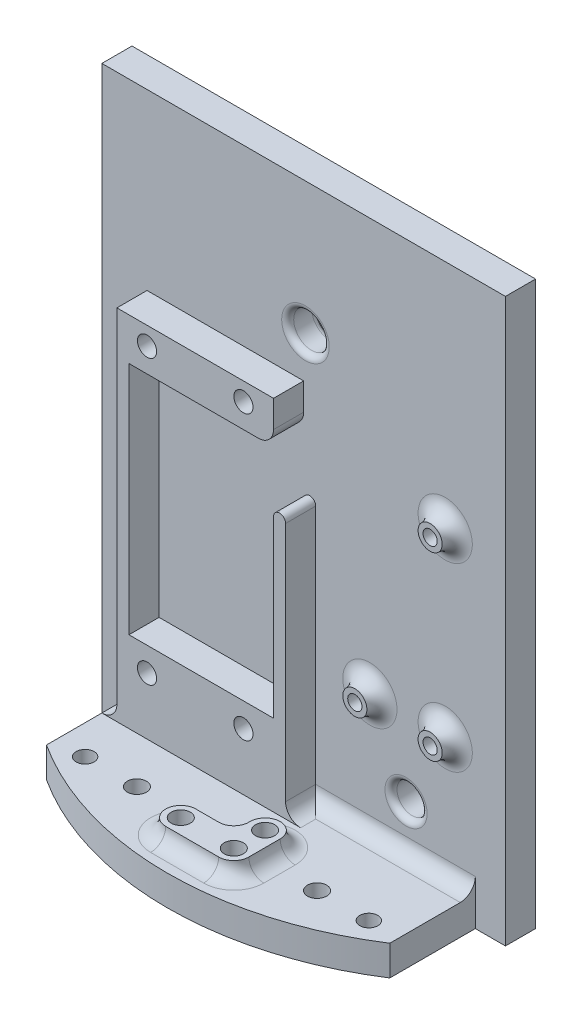
SolidWorks part; units mm, degrees
ref_plane "Front Plane" through (0, 0, 0) normal (0, 0, 1) x (1, 0, 0)
ref_plane "Top Plane" through (0, 0, 0) normal (0, 1, 0) x (1, 0, 0)
ref_plane "Right Plane" through (0, 0, 0) normal (1, 0, 0) x (0, 0, -1)
sketch "Sketch2" plane through (0, 0, 0) normal (0, 0, 1) x (1, 0, 0)
  line L1 (0, 0) -> (85.09, 0)
  line L2 (0, 0) -> (0, 118.618)
  line L3 (0, 118.618) -> (85.09, 118.618)
  line L4 (85.09, 0) -> (85.09, 118.618)
  dimension "D1" = 85.09
  dimension "D2" = 118.618
extrude "Boss1 - Main Figure" add sketch "Sketch2" along normal blind 6.35
sketch "Sketch3" plane through (0, 0, 6.35) normal (0, 0, 1) x (1, 0, 0)
  line L0 (0, 118.618) -> (0, 0) construction
  line L1 (6.35, 6.35) -> (78.74, 6.35)
  line L2 (6.35, 6.35) -> (6.35, 0)
  line L3 (6.35, 0) -> (78.74, 0)
  line L4 (78.74, 6.35) -> (78.74, 0)
  line L5 (85.09, 0) -> (85.09, 118.618) construction
  line L6 (0, 0) -> (85.09, 0) construction
  dimension "D1" = 6.35
  dimension "D2" = 6.35
  dimension "D3" = 0
  dimension "D4" = 6.35
extrude "Boss2 - Bottom Plate" add sketch "Sketch3" along normal blind 18.034
sketch "Sketch4" plane through (0, 0, 0) normal (0, -1, 0) x (1, 0, 0)
  line L2 (6.35, 24.384) -> (78.74, 24.384)
  arc A0 (6.35, 24.384) -> (78.74, 24.384) centre (42.545, -31.7625) cw
  dimension "D2" = 66.802
  dimension "D1" = 0
extrude "Boss3 - Bottom Rounded Cap" add sketch "Sketch4" along direction (0, 1, 0) on the side against the normal up to surface (6.35 mm away) up to face at (42.545, 6.35, 15.367)
sketch "Sketch7" plane through (0, 0, 6.35) normal (0, 0, 1) x (1, 0, 0)
  line L0 (78.74, 6.35) -> (6.35, 6.35) construction
  line L1 (9.525, 6.35) -> (45.085, 6.35)
  line L2 (9.525, 6.35) -> (9.525, 23.495)
  line L3 (12.065, 23.495) -> (42.545, 23.495)
  line L4 (45.085, 6.35) -> (45.085, 23.495)
  line L7 (9.525, 23.495) -> (9.525, 73.025)
  line L9 (12.065, 23.495) -> (12.065, 73.025)
  line L11 (45.085, 23.495) -> (45.085, 60.325)
  line L13 (42.545, 23.495) -> (42.545, 60.325)
  line L14 (12.065, 73.025) -> (39.37, 73.025)
  line L15 (9.525, 73.025) -> (9.525, 81.915)
  line L16 (9.525, 81.915) -> (42.545, 81.915)
  line L17 (42.545, 76.2) -> (42.545, 81.915)
  arc A0 (39.37, 73.025) -> (42.545, 76.2) centre (39.37, 76.2) ccw
  arc A2 (45.085, 60.325) -> (42.545, 60.325) centre (43.815, 60.325) ccw
  dimension "D10" = 3.175
  dimension "D1" = 3.175
  dimension "D2" = 33.655
  dimension "D3" = 17.145
  dimension "D4" = 49.53
  dimension "D5" = 2.54
  dimension "D6" = 36.83
  dimension "D7" = 2.54
  dimension "D8" = 8.89
  dimension "D9" = 33.02
extrude "Boss3 - Card Holder" add sketch "Sketch7" along normal blind 6.35
fillet "Fillet1 - Bottom Plate" radius 3.175 4 edges at (7.9375, 6.35, 6.35) (9.525, 6.35, 9.525) (45.085, 6.35, 9.525) (61.9125, 6.35, 6.35)
hole_wizard "Holes1 - Main Plate" positions "3DSketch3" profile "Sketch14" hole size "#97" standard "ANSI Inch" end condition through all
sketch3d "3DSketch3"
  line L0 (0, 118.618, 0) -> (0, 0, 0) construction
  line L1 (85.09, 118.618, 0) -> (0, 118.618, 0) construction
  point P0 (36.195, 78.105, 0)
  point P2 (15.875, 78.105, 0)
  point P4 (36.195, 18.415, 0)
  point P6 (15.875, 18.415, 0)
  dimension "D1" = 15.875
  dimension "D2" = 20.32
  dimension "D3" = 59.69
  dimension "D4" = 59.69
  dimension "D5" = 15.875
  dimension "D6" = 40.513
  dimension "D7" = 40.513
  dimension "D8" = 20.32
sketch "Sketch14" plane through (36.195, 78.105, 0) normal (1, 0, 0) x (0, 1, 0)
  line L0 (0, 0) -> (0, 35.0395)
  line L1 (0, 35.0395) -> (2.0193, 35.0395)
  line L2 (2.0193, 35.0395) -> (2.0193, 0)
  line L5 (2.0193, 0) -> (0, 0)
  line L11 (0, -6.35) -> (0, 107.95) construction
  dimension "Thru Hole Dia." = 4.0386
  dimension "Thru Hole Depth" = 35.0395
hole_wizard "Holes3 - Upper Large" positions "Sketch26" profile "Sketch27" hole size "1/4" standard "ANSI Inch" end condition through all
sketch "Sketch26" plane through (0, 0, 0) normal (0, 0, -1) x (-1, 0, 0)
  line L0 (0, 118.618) -> (0, 0) construction
  line L1 (-85.09, 118.618) -> (0, 118.618) construction
  point P0 (-42.926, 90.805)
  dimension "D1" = 42.926
  dimension "D2" = 27.813
sketch "Sketch27" plane through (42.926, 90.805, 0) normal (1, 0, 0) x (0, 1, 0)
  line L0 (0, 0) -> (0, 35.0395)
  line L1 (0, 35.0395) -> (3.7465, 35.0395)
  line L2 (3.7465, 35.0395) -> (3.7465, 0)
  line L5 (3.7465, 0) -> (0, 0)
  line L11 (0, -6.35) -> (0, 107.95) construction
  dimension "Thru Hole Dia." = 7.493
  dimension "Thru Hole Depth" = 35.0395
hole_wizard "Holes4 - Lower Large" positions "Sketch28" profile "Sketch29" hole size "1/4" standard "ANSI Inch" end condition through all
sketch "Sketch28" plane through (0, 0, 0) normal (0, 0, -1) x (-1, 0, 0)
  line L0 (0, 0) -> (-85.09, 0) construction
  line L1 (-85.09, 0) -> (-85.09, 118.618) construction
  point P0 (-64.135, 15.875)
  dimension "D1" = 15.875
  dimension "D2" = 20.955
sketch "Sketch29" plane through (64.135, 15.875, 0) normal (1, 0, 0) x (0, 1, 0)
  line L0 (0, 0) -> (0, 35.0395)
  line L1 (0, 35.0395) -> (3.175, 35.0395)
  line L2 (3.175, 35.0395) -> (3.175, 0)
  line L5 (3.175, 0) -> (0, 0)
  line L11 (0, -6.35) -> (0, 107.95) construction
  dimension "Thru Hole Dia." = 6.35
  dimension "Thru Hole Depth" = 35.0395
fillet "Fillet2 - Large Holes" radius 1.27 4 edges at (60.96, 15.875, 6.35) (60.96, 15.875, 0) (39.1795, 90.805, 6.35) (39.1795, 90.805, 0)
hole_wizard "Holes5 - Small Bottom Plate" positions "Sketch30" profile "Sketch31" hole size "1/4" standard "ANSI Inch" end condition through all
sketch "Sketch30" plane through (0, 0, 0) normal (0, -1, 0) x (-1, 0, 0)
  line L0 (-6.35, -24.384) -> (-6.35, -6.35) construction
  line L1 (0, 0) -> (-85.09, 0) construction
  line L2 (-78.74, -24.384) -> (-78.74, -6.35) construction
  point P0 (-23.495, -22.4536)
  point P2 (-61.468, -22.4536)
  dimension "D1" = 17.145
  dimension "D2" = 22.4536
  dimension "D3" = 22.4536
  dimension "D4" = 17.272
sketch "Sketch31" plane through (23.495, 0, 22.4536) normal (1, 0, 0) x (0, 0, -1)
  line L0 (0, 0) -> (0, 118.618)
  line L1 (0, 118.618) -> (2.0193, 118.618)
  line L2 (2.0193, 118.618) -> (2.0193, 0)
  line L5 (2.0193, 0) -> (0, 0)
  line L11 (0, -6.35) -> (0, 107.95) construction
  dimension "Thru Hole Dia." = 4.0386
  dimension "Thru Hole Depth" = 118.618
sketch "Sketch32" plane through (0, 0, 6.35) normal (0, 0, 1) x (1, 0, 0)
  line L0 (85.09, 118.618) -> (0, 118.618) construction
  line L1 (85.09, 0) -> (85.09, 118.618) construction
  circle A0 centre (72.39, 69.85) radius 2.54
  circle A1 centre (56.515, 31.75) radius 2.54
  circle A2 centre (72.39, 31.75) radius 2.54
  point P0 (72.39, 69.85)
  point P1 (72.39, 31.75)
  point P2 (56.515, 31.75)
  dimension "D7" = 5.08
  dimension "D8" = 5.08
  dimension "D9" = 5.08
  dimension "D1" = 48.768
  dimension "D2" = 12.7
  dimension "D3" = 12.7
  dimension "D4" = 38.1
  dimension "D5" = 38.1
  dimension "D6" = 15.875
extrude "Boss4 - Main Plate Standoffs" add sketch "Sketch32" along direction (0, 0, -1) on the side of the normal offset from surface (3.175 mm away) 3.175 up to face at (59.69, 15.875, 6.35) offset beyond the face yes
hole_wizard "Holes5 - Main Plate" positions "Sketch33" profile "Sketch34" hole size "1/4" standard "ANSI Inch" end condition through all
sketch "Sketch33" plane through (0, 0, 9.525) normal (0, 0, 1) x (1, 0, 0)
  point P0 (72.39, 69.85)
  point P3 (72.39, 31.75)
  point P6 (56.515, 31.75)
sketch "Sketch34" plane through (72.39, 69.85, 9.525) normal (1, 0, 0) x (0, -1, 0)
  line L0 (0, 0) -> (0, 9.525)
  line L1 (0, 9.525) -> (1.5, 9.525)
  line L2 (1.5, 9.525) -> (1.5, 0)
  line L5 (1.5, 0) -> (0, 0)
  line L11 (0, -6.35) -> (0, 107.95) construction
  dimension "Thru Hole Dia." = 3
  dimension "Thru Hole Depth" = 9.525
fillet "Fillet3 - Main Plate Standoffs" radius 3.175 3 edges at (53.975, 31.75, 6.35) (69.85, 31.75, 6.35) (69.85, 69.85, 6.35)
sketch "Sketch36" plane through (0, 6.35, 0) normal (0, 1, 0) x (1, 0, 0)
  line L0 (78.74, -24.384) -> (78.74, -9.525) construction
  line L1 (6.35, -24.384) -> (6.35, -12.7) construction
  line L2 (85.09, 0) -> (0, 0) construction
  line L3 (36.957, -23.495) -> (41.783, -23.495)
  line L4 (36.957, -29.845) -> (48.133, -29.845)
  line L5 (44.958, -20.066) -> (44.958, -20.32)
  line L6 (51.308, -26.67) -> (51.308, -20.066)
  arc A0 (44.958, -20.066) -> (51.308, -20.066) centre (48.133, -20.066) cw
  arc A1 (36.957, -23.495) -> (36.957, -29.845) centre (36.957, -26.67) ccw
  arc A2 (51.308, -26.67) -> (48.133, -29.845) centre (48.133, -26.67) cw
  arc A3 (44.958, -20.32) -> (41.783, -23.495) centre (41.783, -20.32) cw
  point P0 (36.957, -26.67)
  point P1 (48.133, -26.67)
  point P2 (48.133, -20.066)
  dimension "D16" = 3.175
  dimension "D1" = 6.604
  dimension "D2" = 30.607
  dimension "D3" = 30.607
  dimension "D4" = 30.607
  dimension "D5" = 26.67
  dimension "D6" = 20.066
  dimension "D7" = 3.175
  dimension "D8" = 3.175
  dimension "D10" = 0
  dimension "D11" = 0
  dimension "D12" = 0
  dimension "D13" = 3.175
  dimension "D15" = 0
  dimension "D14" = 3.175
extrude "Boss5 - Bottom Plate Standoffs" add sketch "Sketch36" along normal blind 3.175
fillet "Fillet4 - Bottom Plate Standoffs" radius 3.175 8 edges at (39.37, 6.35, 23.495) (44.958, 6.35, 20.193) (44.0281, 6.35, 22.5651) (33.782, 6.35, 26.67) (48.133, 6.35, 16.891) (51.308, 6.35, 23.368) (50.3781, 6.35, 28.9151) (42.545, 6.35, 29.845)
hole_wizard "Holes6 - Bottom Plate" positions "Sketch37" profile "Sketch38" hole size "1/4" standard "ANSI Inch" end condition through all
sketch "Sketch37" plane through (0, 9.525, 0) normal (0, 1, 0) x (1, 0, 0)
  line L0 (41.783, -23.495) -> (36.957, -23.495) construction
  arc A0 (36.957, -23.495) -> (36.957, -29.845) centre (36.957, -26.67) ccw construction
  arc A1 (48.133, -29.845) -> (51.308, -26.67) centre (48.133, -26.67) ccw construction
  arc A2 (51.308, -20.066) -> (44.958, -20.066) centre (48.133, -20.066) ccw construction
  point P0 (36.957, -26.67)
  point P2 (48.133, -26.67)
  point P4 (48.133, -20.066)
  dimension "D1" = 0
  dimension "D2" = 3.175
  dimension "D3" = 0
  dimension "D4" = 0
sketch "Sketch38" plane through (36.957, 9.525, 26.67) normal (1, 0, 0) x (0, 0, 1)
  line L0 (0, 0) -> (0, 9.525)
  line L1 (0, 9.525) -> (2.0193, 9.525)
  line L2 (2.0193, 9.525) -> (2.0193, 0)
  line L5 (2.0193, 0) -> (0, 0)
  line L11 (0, -6.35) -> (0, 107.95) construction
  dimension "Thru Hole Dia." = 4.0386
  dimension "Thru Hole Depth" = 9.525
hole_wizard "Holes7" positions "Sketch39" profile "Sketch40" hole size "#6" standard "ANSI Inch" end condition through all
sketch "Sketch39" plane through (0, 6.35, 0) normal (0, 1, 0) x (1, 0, 0)
  circle A0 centre (23.495, -22.4536) radius 2.0193 construction
  circle A1 centre (61.468, -22.4536) radius 2.0193 construction
  point P0 (72.39, -22.4536)
  point P2 (12.573, -22.4536)
  dimension "D1" = 10.922
  dimension "D2" = 10.922
  dimension "D3" = 0
  dimension "D4" = 0
sketch "Sketch40" plane through (72.39, 6.35, 22.4536) normal (1, 0, 0) x (0, 0, 1)
  line L0 (0, 0) -> (0, 6.35)
  line L1 (0, 6.35) -> (1.8986, 6.35)
  line L2 (1.8986, 6.35) -> (1.8986, 0)
  line L5 (1.8986, 0) -> (0, 0)
  line L11 (0, -6.35) -> (0, 107.95) construction
  dimension "Thru Hole Dia." = 3.7973
  dimension "Thru Hole Depth" = 6.35
equation "\"D3@Sketch32\"=\"D2@Sketch32\""
equation "\"D5@Sketch32\"=\"D4@Sketch32\""
equation "\"D8@Sketch32\"=\"D7@Sketch32\""
equation "\"D9@Sketch32\"=\"D7@Sketch32\""
equation "\"D3@Sketch36\"=\"D2@Sketch36\""
equation "\"D4@Sketch36\"=\"D2@Sketch36\""
equation "\"D8@Sketch36\"=\"D7@Sketch36\""
equation "\"D13@Sketch36\"=\"D8@Sketch36\""
equation "\"D14@Sketch36\"=\"D7@Sketch36\""
